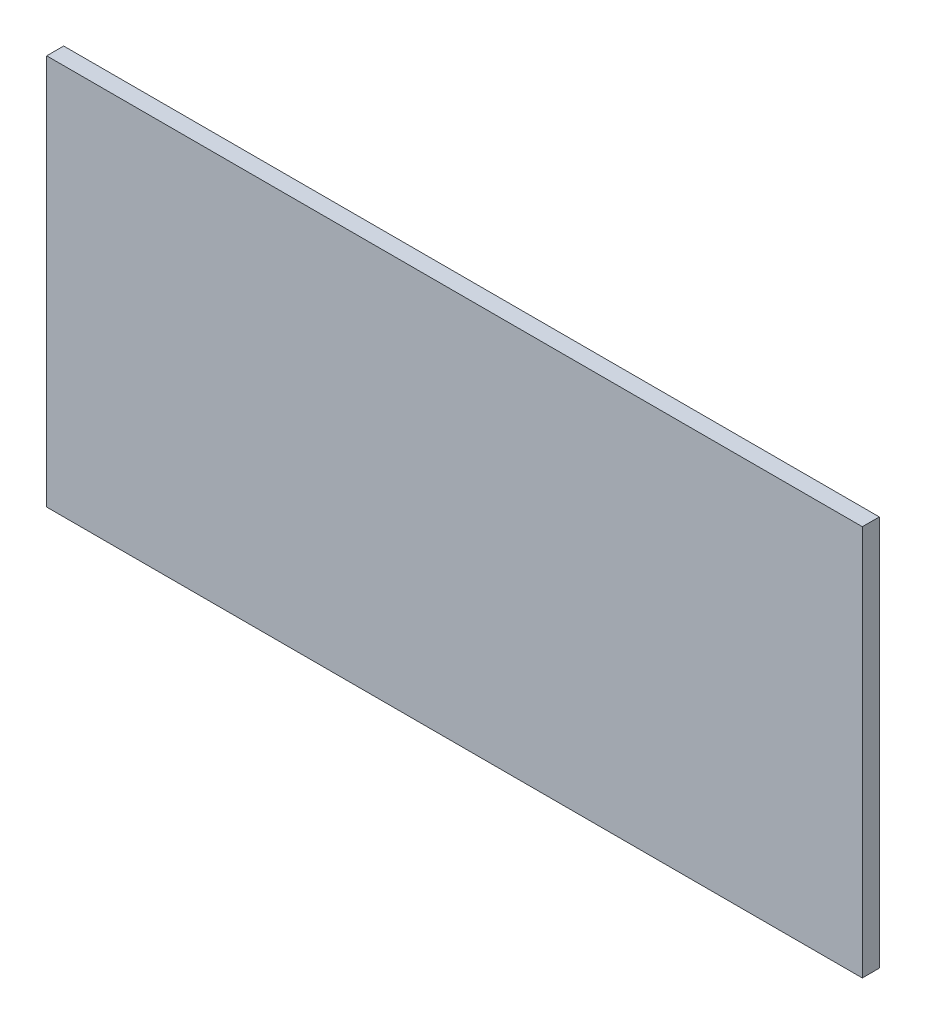
SolidWorks part; units mm, degrees
material "6061-T4 (SS)"
ref_plane "Front Plane" through (0, 0, 0) normal (0, 0, 1) x (1, 0, 0)
ref_plane "Top Plane" through (0, 0, 0) normal (0, 1, 0) x (1, 0, 0)
ref_plane "Right Plane" through (0, 0, 0) normal (1, 0, 0) x (0, 0, -1)
sketch "Sketch1" plane through (0, 0, 0) normal (0, 0, 1) x (1, 0, 0)
  line L1 (0, 0) -> (96, 0)
  line L2 (0, 0) -> (0, 46)
  line L3 (0, 46) -> (96, 46)
  line L4 (96, 0) -> (96, 46)
  dimension "D1" = 46
  dimension "D2" = 96
extrude "Boss-Extrude1" add sketch "Sketch1" along normal blind 2
sketch "Sketch2" plane through (0, 0, 2) normal (0, 0, 1) x (1, 0, 0)
  circle A0 centre (75.2, 23.05) radius 13.1445
  circle A1 centre (75.2, 23.05) radius 13.1445 construction
extrude "Cut-Extrude1" [suppressed] cut sketch "Sketch2" against normal through all
